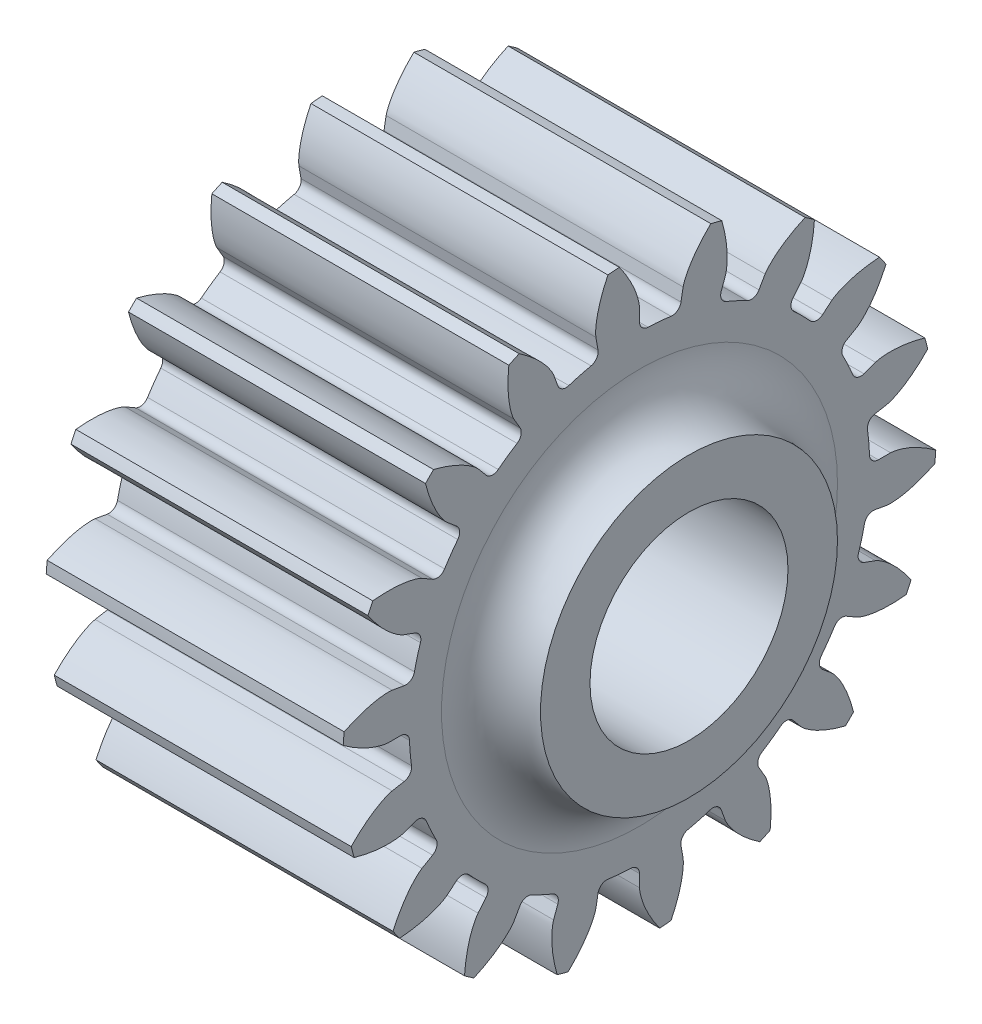
SolidWorks part; units mm, degrees
note: The reader was unsure of these and kept them because the rebuilt part matched: shared geometry of "Sketch4<5>".
ref_plane "Front Plane" through (0, 0, 0) normal (1, 0, 0) x (0, 1, 0)
ref_plane "Top Plane" through (0, 0, 0) normal (0, 0, 1) x (0, 1, 0)
ref_plane "Right Plane" through (0, 0, 0) normal (0, 1, 0) x (-1, 0, 0)
sketch "rooot" plane through (0, 0, 0) normal (1, 0, 0) x (0, 1, 0)
  circle A0 centre (0, 0) radius 23.25 construction
  circle A1 centre (0, 0) radius 24 construction
  circle A2 centre (0, 0) radius 30 construction
  circle A3 centre (0, 0) radius 25.37 construction
  dimension "D1" = 46.5
  dimension "D2" = 48
  dimension "D3" = 60
  dimension "D4" = 50.74
sketch "Sketch4" plane through (0, 0, 0) normal (1, 0, 0) x (0, 1, 0)
  line L0 (0, 0) -> (0, 25.3717)
  line L1 (0, 0) -> (2.6147, 29.8858)
  circle A0 centre (0, 0) radius 30 construction
  circle A1 centre (0, 0) radius 30
  circle A2 centre (0, 0) radius 25.37 construction
  circle A3 centre (0, 0) radius 25.37
  circle A4 centre (0, 0) radius 23.25 construction
  circle A5 centre (0, 0) radius 23.25
  spline S0 degree 4 poles (0, 25.3717) (0.0015, 25.418) (0.0106, 25.5475) (0.0465, 25.7908) (0.1314, 26.1832) (0.2778, 26.6744) (0.5101, 27.2958) (0.8378, 28.0076) (1.2531, 28.7647) (1.8894, 29.7558) (2.7489, 30.8801) (3.8415, 32.0723) (5.2125, 33.3178) (6.6814, 34.4456) (8.2314, 35.4588) (10.2925, 36.6031) (12.2344, 37.4628) (14.01, 38.0998) (15.5922, 38.5651) (16.5034, 38.805) (17.6506, 39.0729) (18.8068, 39.2988) (19.9705, 39.4836) (21.373, 39.6569) (22.4298, 39.7512) (23.3692, 39.8079) (24.1955, 39.8374) (24.6557, 39.8487) (25.2631, 39.8552) (25.7488, 39.8535) (26.6221, 39.8397) (27.2628, 39.8094) (27.9577, 39.7754) (28.2808, 39.7479) (28.5055, 39.7329) knots 0 0 0 0 0 0.005377 0.015084 0.028532 0.04661 0.064855 0.092111 0.119476 0.146842 0.201575 0.256307 0.307035 0.361767 0.4165 0.471232 0.580697 0.608063 0.635429 0.662795 0.690161 0.744894 0.77226 0.799626 0.854358 0.868042 0.881725 0.895408 0.909091 0.931818 0.954545 0.977273 1 1 1 1 1 construction
  spline S1 degree 4 poles (0, 25.3717) (0.0015, 25.418) (0.0106, 25.5475) (0.0465, 25.7908) (0.1314, 26.1832) (0.2778, 26.6744) (0.5101, 27.2958) (0.8378, 28.0076) (1.2531, 28.7647) (1.8894, 29.7558) (2.7489, 30.8801) (3.8415, 32.0723) (5.2125, 33.3178) (6.6814, 34.4456) (8.2314, 35.4588) (10.2925, 36.6031) (12.2344, 37.4628) (14.01, 38.0998) (15.5922, 38.5651) (16.5034, 38.805) (17.6506, 39.0729) (18.8068, 39.2988) (19.9705, 39.4836) (21.373, 39.6569) (22.4298, 39.7512) (23.3692, 39.8079) (24.1955, 39.8374) (24.6557, 39.8487) (25.0467, 39.8528) (25.2646, 39.8538) (25.3717, 39.8538) knots 0 0 0 0 0 0.005377 0.015084 0.028532 0.04661 0.064855 0.092111 0.119476 0.146842 0.201575 0.256307 0.307035 0.361767 0.4165 0.471232 0.580697 0.608063 0.635429 0.662795 0.690161 0.744894 0.77226 0.799626 0.854358 0.868042 0.881725 0.895408 0.909091 0.909091 0.909091 0.909091 0.909091
  dimension "D1" = 5
extrude "Boss-Extrude1" add sketch "Sketch4" along normal blind 30 contours S1 L0 A3 L1 A1 | A5 L1 A3 L0
extrude "Boss-Extrude2" add sketch "Sketch4<5>" along normal blind 30 contours L0 A5 L1 | L1 A5 L0
sketch "Sketch4<5>" plane through (0, 0, 0) normal (1, 0, 0) x (0, 1, 0) same geometry as "Sketch4"
mirror "Mirror1" about plane through (30, 0, 0) normal (0, -0.9962, 0.0872) of "Boss-Extrude2"
mirror "Mirror2" about plane through (30, 0, 0) normal (0, -0.9962, 0.0872) of "Boss-Extrude1"
fillet "Fillet1" radius 0.9 2 edges at (15, 0, 23.25) (15, 4.0373, 22.8968)
pattern_circular "CirPattern1" count 18 over 360 about axis through (30, 0, 0) along (-1, 0, 0) of "Boss-Extrude1", "Mirror2", "Fillet1"
sketch "Sketch5" plane through (30, 0, 0) normal (1, 0, 0) x (0, 1, 0)
  circle A0 centre (0, 0) radius 10
  circle A1 centre (0, 0) radius 15
  dimension "D1" = 20
  dimension "D2" = 5
extrude "Boss-Extrude5" add sketch "Sketch5" along normal blind 5
sketch "Sketch10" plane through (30, 0, 0) normal (1, 0, 0) x (0, 1, 0)
  circle A0 centre (0, 0) radius 10
extrude "Cut-Extrude5" cut sketch "Sketch10" against normal through all
sketch "Sketch13" plane through (0, 0, 0) normal (-1, 0, 0) x (0, -1, 0)
  circle A0 centre (0, 0) radius 15
  circle A1 centre (0, 0) radius 10
  dimension "D1" = 30
extrude "Boss-Extrude6" add sketch "Sketch13" along normal blind 5
fillet "Fillet4" radius 5 2 edges at (30, 0, -15) (0, 0, -15)
equation "\"N\"= 18"
equation "\"M\"= 3"
equation "\"Pitch\"= \"M\" * \"N\""
equation "\"BaseDIA\"= \"Pitch\" * cos ( 20 )"
equation "\"OuterDIA\"= \"Pitch\" + 2 * \"M\""
equation "\"RootDIA\"= \"Pitch\" - 2.5 * \"M\""
equation "\"ClearanceDIA\"= \"Pitch\" - 2 * \"M\""
equation "\"BR\"= \"BaseDIA\" / 2"
equation "\"RFR\"= 0.3 * \"M\""
